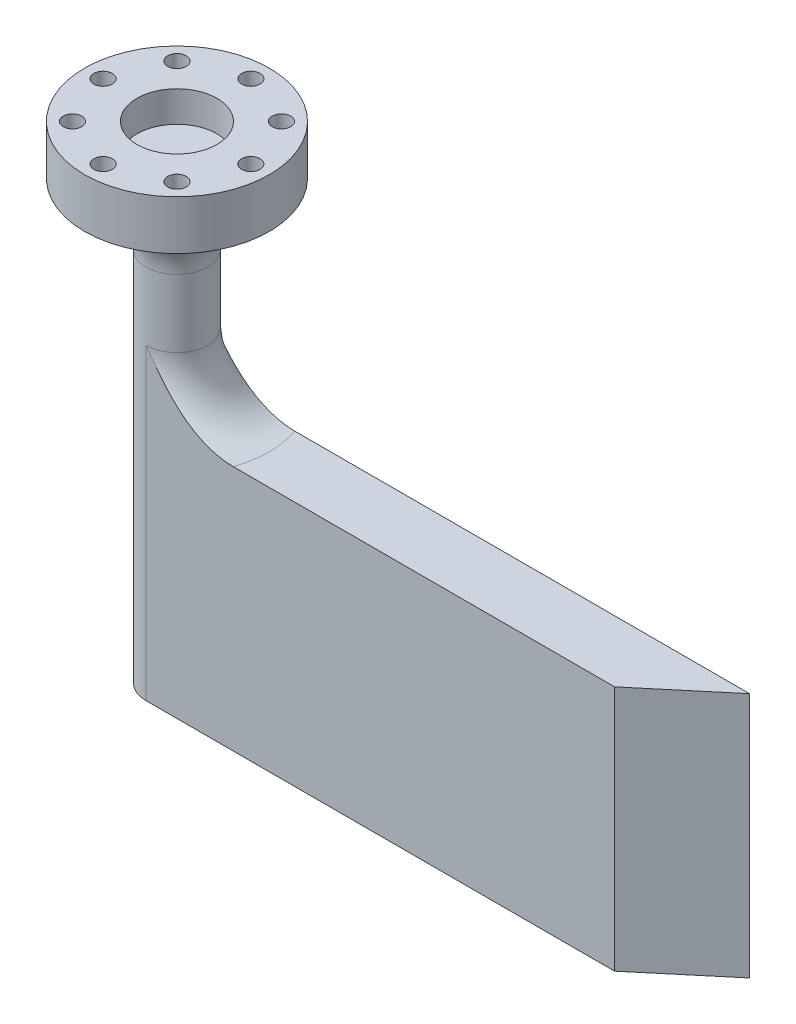
SolidWorks part; units mm, degrees
ref_plane "Front Plane" through (0, 0, 0) normal (0, 0, 1) x (1, 0, 0)
ref_plane "Top Plane" through (0, 0, 0) normal (0, 1, 0) x (1, 0, 0)
ref_plane "Right Plane" through (0, 0, 0) normal (1, 0, 0) x (0, 0, -1)
sketch "Sketch1" plane through (0, 0, 0) normal (0, 0, 1) x (1, 0, 0)
  line L0 (0, -16.5) -> (0, 16.5) construction
  line L1 (0, 20) -> (88, 20)
  line L2 (0, 20) -> (0, -20)
  line L3 (0, -20) -> (88, -20)
  line L4 (88, 20) -> (88, -20)
  dimension "D1" = 88
  dimension "D2" = 40
  dimension "D3" = 20
extrude "Boss-Extrude1" add sketch "Sketch1" against normal mid plane 10
sketch "Sketch3" plane through (0, 0, 0) normal (0, 1, 0) x (1, 0, 0)
  circle A0 centre (0, 0) radius 5
  dimension "D1" = 10
sketch "Sketch4" plane through (0, -20, 0) normal (0, -1, 0) x (1, 0, 0)
  circle A0 centre (0, 0) radius 5
  dimension "D1" = 10
extrude "Boss-Extrude2" add sketch "Sketch4" against normal blind 71
sketch "Sketch5" plane through (0, 51, 0) normal (0, 1, 0) x (1, 0, 0)
  circle A0 centre (0, 0) radius 15
  circle A1 centre (0, 0) radius 12 construction
  circle A2 centre (0, 12) radius 1.5
  circle A3 centre (8.4853, 8.4853) radius 1.5
  circle A4 centre (12, 0) radius 1.5
  circle A5 centre (8.4853, -8.4853) radius 1.5
  circle A6 centre (0, -12) radius 1.5
  circle A7 centre (-8.4853, -8.4853) radius 1.5
  circle A8 centre (-12, 0) radius 1.5
  circle A9 centre (-8.4853, 8.4853) radius 1.5
  point P22 (0, 0)
  dimension "D1" = 30
  dimension "D2" = 24
  dimension "D3" = 3
  dimension "D4" = 8
extrude "Boss-Extrude3" add sketch "Sketch5" along normal blind 8
sketch "Sketch6" plane through (0, 59, 0) normal (0, 1, 0) x (1, 0, 0)
  circle A0 centre (0, 0) radius 6.5
  dimension "D1" = 13
extrude "Cut-Extrude1" cut sketch "Sketch6" against normal blind 5
fillet "Fillet1" radius 10 1 edges at (0, 51, -5)
fillet "Fillet2" radius 10 1 edges at (5, 20, 0)
ref_plane "Plane1" through (0, 54, 0) normal (0, 1, 0) x (1, 0, 0)
sketch "Sketch7" plane through (0, 54, 0) normal (0, 1, 0) x (1, 0, 0)
  circle A0 centre (0, 0) radius 12
  circle A1 centre (0, 12) radius 2.5
  circle A9 centre (8.4853, 8.4853) radius 2.5
  circle A10 centre (12, 0) radius 2.5
  circle A11 centre (8.4853, -8.4853) radius 2.5
  circle A12 centre (0, -12) radius 2.5
  circle A13 centre (-8.4853, -8.4853) radius 2.5
  circle A14 centre (-12, 0) radius 2.5
  circle A15 centre (-8.4853, 8.4853) radius 2.5
  point P22 (1.2071, 0.5)
  point P23 (0, 0)
  dimension "D1" = 5
  dimension "D2" = 8
extrude "Cut-Extrude2" cut sketch "Sketch7" against normal blind 7 contours A0 A9 | A0 A1 | A0 A9 | A0 A1 | A0 A10 | A0 A10 | A0 A15 | A0 A15 | A0 A11 | A0 A11 | A0 A12 | A0 A12 | A0 A14 | A0 A14 | A0 A13 | A0 A13 region at (10.8935, 54, 0) region at (13.0128, 54, 0) region at (7.7028, 54, -7.7028) region at (9.2014, 54, -9.2014) region at (9.2014, 54, 9.2014) region at (7.7028, 54, 7.7028) region at (0, 54, -10.8935) region at (0, 54, -13.0128) region at (0, 54, 13.0128) region at (0, 54, 10.8935) region at (-7.7028, 54, -7.7028) region at (-9.2014, 54, -9.2014) region at (-9.2014, 54, 9.2014) region at (-7.7028, 54, 7.7028) region at (-10.8935, 54, 0) region at (-13.0128, 54, 0)
chamfer "Chamfer1" distance 10 angle 50 1 edges at (88, 0, 5) first distance on face at (88, 0, 0)
